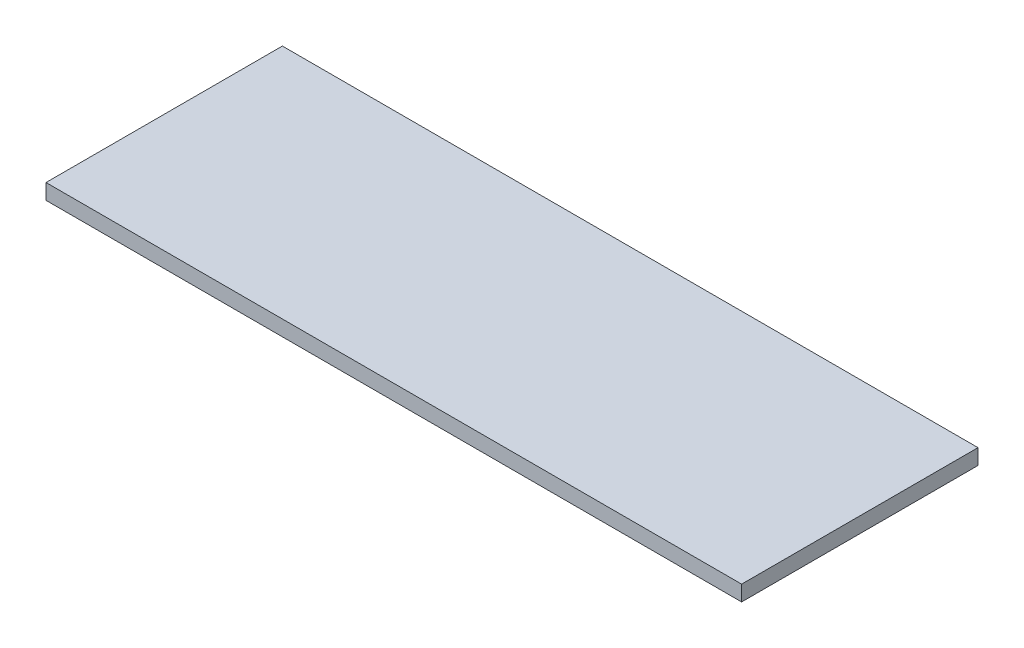
SolidWorks part; units mm, degrees
ref_plane "Front Plane" through (0, 0, 0) normal (0, 0, 1) x (1, 0, 0)
ref_plane "Top Plane" through (0, 0, 0) normal (0, 1, 0) x (1, 0, 0)
ref_plane "Right Plane" through (0, 0, 0) normal (1, 0, 0) x (0, 0, -1)
sketch "Sketch1" plane through (0, 0, 0) normal (0, 1, 0) x (1, 0, 0)
  line L1 (0, 0) -> (54, 0)
  line L2 (0, 0) -> (0, 18.35)
  line L3 (0, 18.35) -> (54, 18.35)
  line L4 (54, 0) -> (54, 18.35)
  dimension "D1" = 54
  dimension "D2" = 18.35
extrude "Boss-Extrude1" add sketch "Sketch1" along normal blind 1.2
